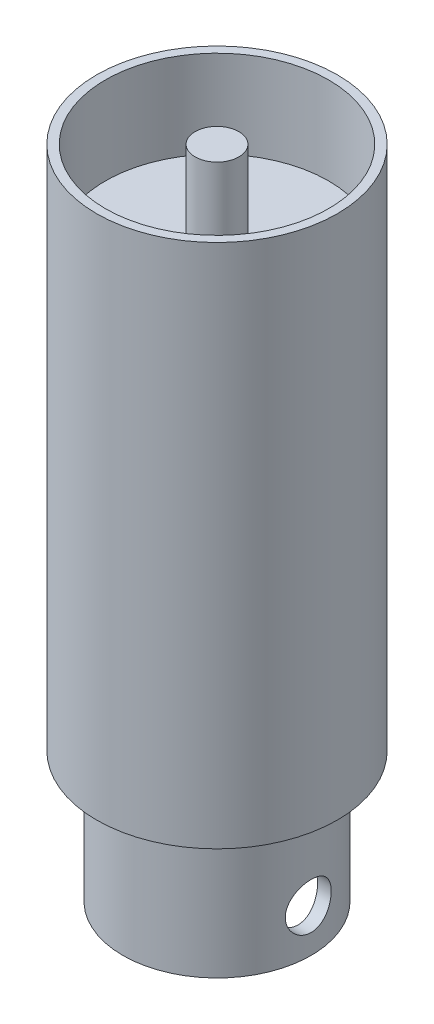
SolidWorks part; units mm, degrees
ref_plane "Front Plane" through (0, 0, 0) normal (0, 0, 1) x (1, 0, 0)
ref_plane "Top Plane" through (0, 0, 0) normal (0, 1, 0) x (1, 0, 0)
ref_plane "Right Plane" through (0, 0, 0) normal (1, 0, 0) x (0, 0, -1)
sketch "Sketch1" plane through (0, 0, 0) normal (0, 1, 0) x (1, 0, 0)
  circle A0 centre (0, 0) radius 13.75
  dimension "D1" = 27.5
extrude "Boss-Extrude1" add sketch "Sketch1" along normal blind 60
sketch "Sketch5" plane through (0, 0, 0) normal (0, -1, 0) x (1, 0, 0)
  line L1 (-0.75, -9.25) -> (0.75, -9.25)
  line L2 (-0.75, -9.25) -> (-0.75, 9.25)
  line L3 (-0.75, 9.25) -> (0.75, 9.25)
  line L4 (0.75, -9.25) -> (0.75, 9.25)
  line L5 (-0.75, -9.25) -> (0.75, 9.25) construction
  line L6 (-0.75, 9.25) -> (0.75, -9.25) construction
  circle A0 centre (0, 0) radius 10.75
  circle A1 centre (0, 0) radius 13.75 construction
  circle A2 centre (0, 0) radius 9.25
  dimension "D1" = 3
  dimension "D2" = 1.5
  dimension "D3" = 1.5
extrude "Boss-Extrude2" add sketch "Sketch5" along normal blind 14.9 contours A0 A2 L4 L1 L2 L3 | L4 A2 L2 | A2 L3 L2 | A2 L4 L3 | A2 L2 L1 | A2 L1 L4 region at (-0.5626, 0, -9.2409) region at (0.5626, 0, -9.2409) region at (0, 0, 0) region at (-0.5626, 0, 9.2409) region at (0.5626, 0, 9.2409) region at (-10.4459, 0, 0)
sketch "Sketch6" plane through (0, 0, 0) normal (0, -1, 0) x (1, 0, 0)
  line L0 (-0.75, 9.2195) -> (-0.75, -9.2195)
  line L1 (0.75, 9.2195) -> (0.75, -9.2195)
  circle A0 centre (0, 0) radius 9.25
  line M2 (-0.75, -9.2195) -> (-0.75, 9.2195)
  arc M3 (-0.75, 9.2195) -> (-0.75, -9.2195) centre (0, 0) ccw
extrude "Cut-Extrude1" cut sketch "Sketch6" against normal blind 20 contours M3 M2 | L1 A0 region at (-4.3341, 0, 0) region at (4.3341, 0, 0)
sketch "Sketch7" plane through (0, 0, 0) normal (1, 0, 0) x (0, 0, -1)
  line L0 (0, -27.237) -> (0, -26.1789) construction
  circle A0 centre (0, -10) radius 2.625
  dimension "D2" = 5.25
  dimension "D1" = 10
extrude "Cut-Extrude2" cut sketch "Sketch7" against normal through all both and the other way through all
sketch "Sketch8" plane through (0, 0, 0) normal (1, 0, 0) x (0, 0, -1)
  circle A0 centre (0, -10) radius 2.625
  dimension "D1" = 5.25
extrude "Boss-Extrude3" add sketch "Sketch8" along normal up to surface and the other way up to surface up to face at (0.75, -10, 2.625) other way up to face at (-0.75, -10, 2.625)
sketch "Sketch9" plane through (0, 60, 0) normal (0, 1, 0) x (1, 0, 0)
  circle A0 centre (0, 0) radius 12.75
  circle A1 centre (0, 0) radius 13.75 construction
  circle A2 centre (0, 0) radius 2.5
  dimension "D1" = 1
  dimension "D2" = 5
  dimension "D3" = 25.5
extrude "Cut-Extrude3" cut sketch "Sketch9" against normal blind 10 contours A0 A2 region at (-12.3894, 60, 0)
